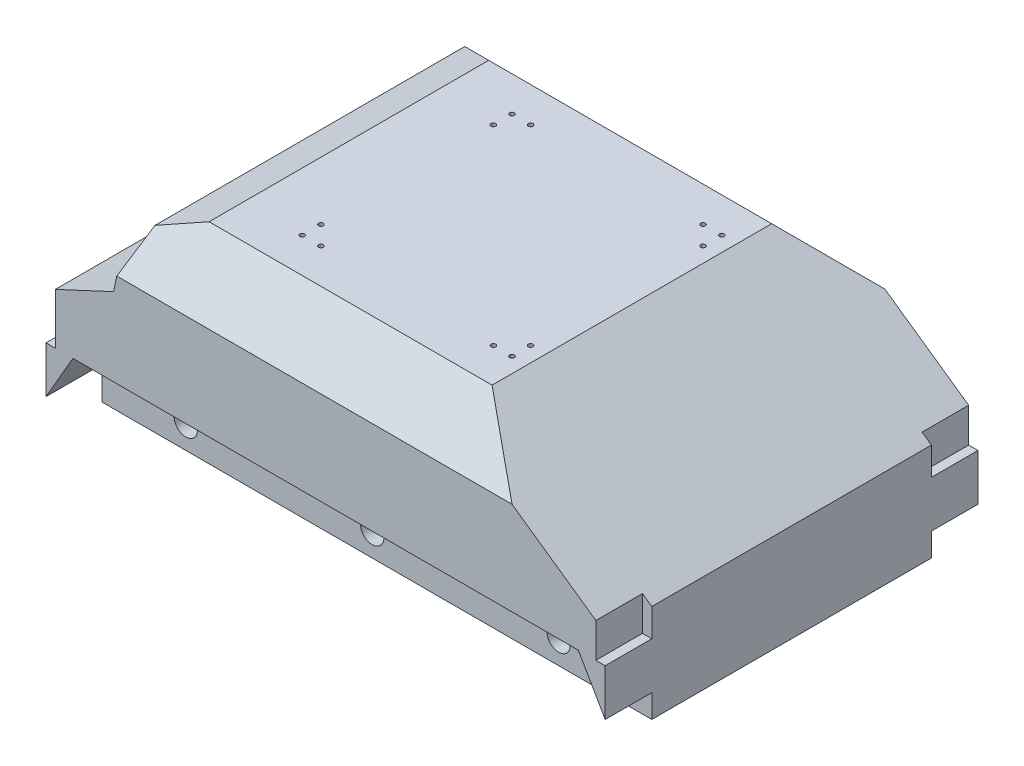
SolidWorks part; units mm, degrees
ref_plane "Front Plane" through (0, 0, 0) normal (0, 0, 1) x (1, 0, 0)
ref_plane "Top Plane" through (0, 0, 0) normal (0, 1, 0) x (1, 0, 0)
ref_plane "Right Plane" through (0, 0, 0) normal (1, 0, 0) x (0, 0, -1)
sketch "Sketch1" plane through (44.2247, 74.8917, 130.2829) normal (0, 1, 0) x (1, 0, 0)
  line L0 (-73.66, -50.8) -> (-73.66, -19.05)
  line L1 (-73.66, -19.05) -> (-76.2, -19.05)
  line L2 (-76.2, -19.05) -> (-76.2, 19.05)
  line L3 (-76.2, 19.05) -> (-73.66, 19.05)
  line L4 (-73.66, 19.05) -> (-73.66, 50.8)
  line L5 (-73.66, 50.8) -> (73.66, 50.8)
  line L6 (73.66, 50.8) -> (73.66, 38.1)
  line L7 (73.66, 38.1) -> (76.2, 38.1)
  line L8 (76.2, 38.1) -> (76.2, -38.1)
  line L9 (76.2, -38.1) -> (73.66, -38.1)
  line L10 (73.66, -38.1) -> (73.66, -50.8)
  line L11 (73.66, -50.8) -> (-73.66, -50.8)
extrude "Boss-Extrude1" add sketch "Sketch1" along normal blind 38.1
sketch "Sketch2" plane through (44.2247, 74.8917, 130.2829) normal (0, 0, 1) x (1, 0, 0)
  line L0 (-76.2, 12.7) -> (-57.7838, 21.2876)
  line L1 (-76.2, 38.1) -> (-76.2, 0) construction
  line L2 (-57.7838, 21.2876) -> (-55.0844, 33.9876)
  line L3 (-55.0844, 33.9876) -> (-44.45, 38.1)
  line L4 (-73.66, 38.1) -> (73.66, 38.1) construction
  line L5 (-44.45, 38.1) -> (-76.2, 38.1)
  line L6 (-76.2, 38.1) -> (-76.2, 12.7)
  line L7 (32.67, 38.1) -> (76.2, 7.62)
  line L8 (76.2, 38.1) -> (76.2, 0) construction
  line L9 (76.2, 7.62) -> (76.2, 38.1)
  line L10 (76.2, 38.1) -> (32.67, 38.1)
  line L11 (-73.66, 0) -> (73.66, 0) construction
  dimension "D1" = 25
  dimension "D2" = 20.32
  dimension "D3" = 25.4
  dimension "D4" = 31.75
  dimension "D5" = 12.7
  dimension "D6" = 12
  dimension "D7" = 35
  dimension "D8" = 30.48
extrude "Cut-Extrude1" cut sketch "Sketch2" against normal through all and the other way through all
sketch "Sketch3" plane through (44.2247, 74.8917, 130.2829) normal (0, 0, 1) x (1, 0, 0)
  line L0 (-76.2, 0) -> (-76.2, -12.7)
  line L1 (-76.2, -12.7) -> (-68.8677, 0)
  line L2 (-73.66, 0) -> (73.66, 0) construction
  line L3 (-68.8677, 0) -> (-76.2, 0)
  line L4 (76.2, 0) -> (76.2, -12.7)
  line L5 (76.2, -12.7) -> (68.8677, 0)
  line L6 (-73.66, 0) -> (73.66, 0) construction
  line L7 (68.8677, 0) -> (76.2, 0)
  dimension "D1" = 12.7
  dimension "D2" = 30
  dimension "D3" = 30
extrude "Boss-Extrude2" add sketch "Sketch3" along normal up to surface and the other way up to surface up to face at (28.6437, 94.2364, 181.0829) other way up to face at (28.6437, 94.2364, 79.4829)
sketch "Sketch4" plane through (44.2247, 74.8917, 130.2829) normal (1, 0, 0) x (0, 0, -1)
  line L0 (-38.1, 38.1) -> (-50.8, 25.4)
  line L1 (50.8, 38.1) -> (-50.8, 38.1) construction
  line L2 (-50.8, 38.1) -> (-50.8, 9.3985) construction
  line L3 (-50.8, 25.4) -> (-50.8, 38.1)
  line L4 (-50.8, 38.1) -> (-38.1, 38.1)
  line L5 (0, 38.1) -> (0, -12.7) construction
  line L6 (-50.8, -12.7) -> (50.8, -12.7) construction
  line L7 (38.1, 38.1) -> (50.8, 25.4)
  line L8 (50.8, 38.1) -> (38.1, 38.1)
  line L9 (50.8, 25.4) -> (50.8, 38.1)
  dimension "D1" = 12.7
  dimension "D2" = 45
extrude "Cut-Extrude2" cut sketch "Sketch4" against normal through all and the other way through all
sketch "Sketch5" plane through (0, 74.8917, 0) normal (0, -1, 0) x (1, 0, 0)
  line L1 (-29.4353, 168.3829) -> (120.4247, 168.3829)
  line L2 (-29.4353, 168.3829) -> (-29.4353, 92.1829)
  line L3 (-29.4353, 92.1829) -> (120.4247, 92.1829)
  line L4 (120.4247, 168.3829) -> (120.4247, 92.1829)
extrude "Boss-Extrude4" add sketch "Sketch5" along normal blind 19.05
sketch "Sketch6" plane through (0, 0, 92.1829) normal (0, 0, -1) x (-1, 0, 0)
  line L0 (-95.0247, 62.1917) -> (6.5753, 62.1917) construction
  circle A0 centre (-95.0247, 62.1917) radius 3.175
  circle A1 centre (-44.2247, 62.1917) radius 3.175
  circle A2 centre (6.5753, 62.1917) radius 3.175
  circle A3 centre (-95.0247, 62.1917) radius 3.175 construction
  point P0 (-44.2247, 62.1917)
extrude "Cut-Extrude3" cut sketch "Sketch6" against normal through all
sketch "Sketch7" plane through (-39.2605, 84.1945, 0) normal (-0.4226, 0.9063, 0) x (0.9063, 0.4226, 0)
  line L1 (12.0049, -115.8442) -> (25.6266, -115.8442)
  line L2 (12.0049, -115.8442) -> (12.0049, -145.1415)
  line L3 (12.0049, -145.1415) -> (25.6266, -145.1415)
  line L4 (25.6266, -115.8442) -> (25.6266, -145.1415)
extrude "Cut-Extrude4" cut sketch "Sketch7" against normal blind 2.54
shell "Shell1" thickness 2.54 removed face at (-21.1342, 89.8443, 130.4928)
sketch "Top to Base Interface Sketch" plane through (0, 112.9917, 0) normal (0, 1, 0) x (1, 0, 0)
  circle A0 centre (15.6497, -101.7079) radius 0.635
  circle A1 centre (15.6497, -106.7879) radius 0.635
  circle A2 centre (20.7297, -101.7079) radius 0.635
  circle A3 centre (72.7997, -101.7079) radius 0.635
  circle A4 centre (72.7997, -106.7879) radius 0.635
  circle A5 centre (67.7197, -101.7079) radius 0.635
  circle A6 centre (72.7997, -158.8579) radius 0.635
  circle A7 centre (72.7997, -153.7779) radius 0.635
  circle A8 centre (67.7197, -158.8579) radius 0.635
  circle A9 centre (15.6497, -158.8579) radius 0.635
  circle A10 centre (15.6497, -153.7779) radius 0.635
  circle A11 centre (20.7297, -158.8579) radius 0.635
extrude "Cut-Extrude5" cut sketch "Top to Base Interface Sketch" against normal blind 12.7
